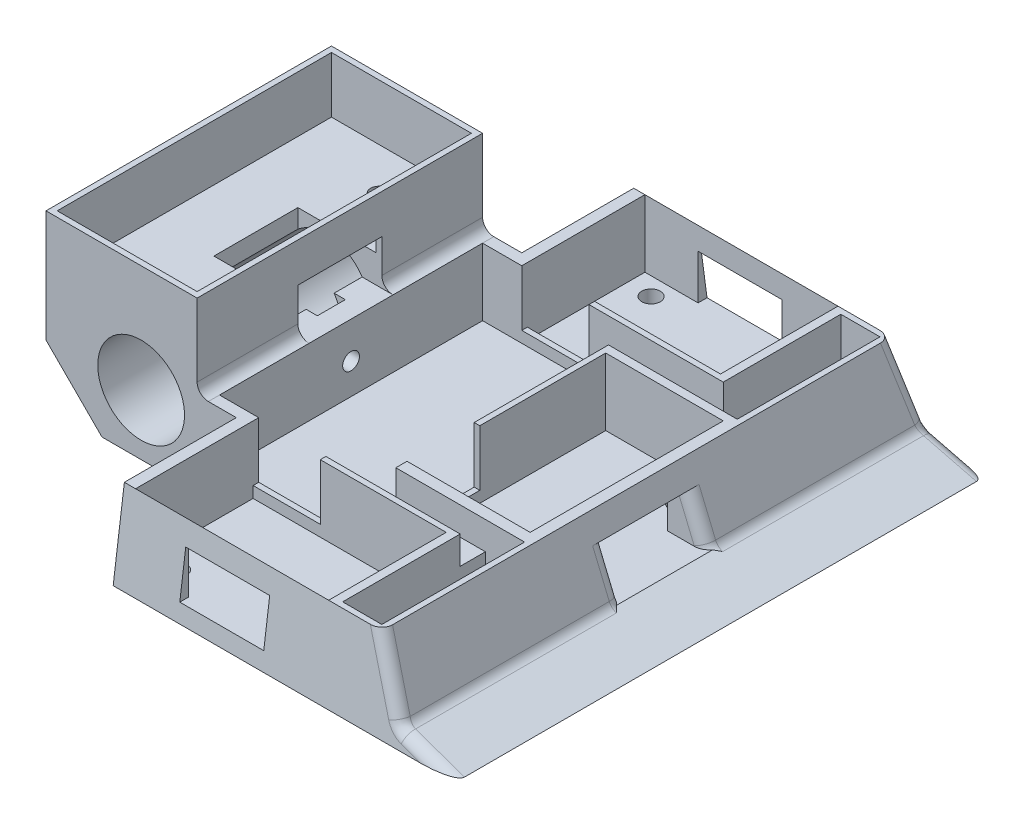
SolidWorks part; units mm, degrees
ref_plane "Front Plane" through (0, 0, 0) normal (0, 0, 1) x (1, 0, 0)
ref_plane "Top Plane" through (0, 0, 0) normal (0, 1, 0) x (1, 0, 0)
ref_plane "Right Plane" through (0, 0, 0) normal (1, 0, 0) x (0, 0, -1)
sketch "Sketch1" plane through (0, 0, 0) normal (0, 1, 0) x (1, 0, 0)
  line L1 (-26.0319, 60.4179) -> (68.9681, 60.4179)
  line L2 (-26.0319, 60.4179) -> (-26.0319, -34.5821)
  line L3 (-26.0319, -34.5821) -> (68.9681, -34.5821)
  line L4 (68.9681, 60.4179) -> (68.9681, -34.5821)
  dimension "D1" = 95
  dimension "D2" = 95
extrude "Boss-Extrude1" add sketch "Sketch1" along normal blind 20
sketch "Sketch2" plane through (0, 0, 34.5821) normal (0, 0, 1) x (1, 0, 0)
  line L0 (-26.0319, 20) -> (68.9681, 20) construction
  line L1 (-26.0319, 0) -> (7.9681, 0)
  line L2 (-26.0319, 0) -> (-26.0319, 20)
  line L3 (-26.0319, 20) -> (7.9681, 20)
  line L4 (7.9681, 0) -> (7.9681, 20)
  dimension "D1" = 34
extrude "Cut-Extrude1" cut sketch "Sketch2" against normal blind 22
sketch "Sketch3" plane through (0, 0, -60.4179) normal (0, 0, -1) x (-1, 0, 0)
  line L0 (-68.9681, 20) -> (26.0319, 20) construction
  line L1 (26.0319, 0) -> (-7.9681, 0)
  line L2 (26.0319, 0) -> (26.0319, 20)
  line L3 (26.0319, 20) -> (-7.9681, 20)
  line L4 (-7.9681, 0) -> (-7.9681, 20)
  dimension "D1" = 34
extrude "Cut-Extrude2" cut sketch "Sketch3" against normal blind 22
sketch "Sketch4" plane through (0, 0, -38.4179) normal (0, 0, -1) x (-1, 0, 0)
  line L0 (-7.9681, 0) -> (26.0319, 0) construction
  line L1 (26.0319, 0) -> (26.0319, 20) construction
  circle A0 centre (9.0319, 10.75) radius 7.75
  dimension "D1" = 10.75
  dimension "D2" = 17
extrude "Cut-Extrude3" cut sketch "Sketch4" against normal blind 100
sketch "Sketch5" plane through (0, 0, -60.4179) normal (0, 0, -1) x (-1, 0, 0)
  line L0 (-7.9681, 20) -> (-7.9681, 0) construction
  line L1 (-68.9681, 20) -> (-7.9681, 20)
  line L2 (-68.9681, 20) -> (-68.9681, 15)
  line L3 (-68.9681, 15) -> (-7.9681, 15)
  line L4 (-7.9681, 20) -> (-7.9681, 15)
  dimension "D1" = 5
extrude "Cut-Extrude4" cut sketch "Sketch5" against normal blind 100
fillet "Fillet3" radius 2 2 edges at (7.9681, 15, -12.9179) (7.9681, 20, -12.9179)
sketch "Sketch7" plane through (68.9681, 0, 0) normal (1, 0, 0) x (0, 0, -1)
  line L0 (-34.5821, 0) -> (60.4179, 0) construction
  line L1 (5.4179, 3) -> (20.4179, 3)
  line L2 (5.4179, 3) -> (5.4179, 11)
  line L3 (5.4179, 11) -> (20.4179, 11)
  line L4 (20.4179, 3) -> (20.4179, 11)
  line L5 (-34.5821, 15) -> (-34.5821, 0) construction
  line L6 (60.4179, 15) -> (60.4179, 0) construction
  dimension "D1" = 15
  dimension "D2" = 8
  dimension "D3" = 3
  dimension "D4" = 40
  dimension "D5" = 40
extrude "Cut-Extrude7" cut sketch "Sketch7" against normal blind 50
sketch "Sketch8" plane through (0, 0, 34.5821) normal (0, 0, 1) x (1, 0, 0)
  line L0 (68.9681, 0) -> (58.9681, 3)
  line L1 (58.9681, 3) -> (53.9681, 15)
  line L2 (68.9681, 15) -> (7.9681, 15) construction
  line L3 (53.9681, 15) -> (68.9681, 15)
  line L4 (68.9681, 15) -> (68.9681, 0)
  line L6 (7.9681, 0) -> (68.9681, 0) construction
  dimension "D1" = 15
  dimension "D2" = 10
  dimension "D3" = 3
extrude "Cut-Extrude8" cut sketch "Sketch8" against normal blind 100
fillet "Fillet4" radius 2 1 edges at (58.9681, 3, 14.5821)
fillet "Fillet5" radius 2 1 edges at (58.9681, 3, -40.4179)
sketch "Sketch10" plane through (0, 15, 0) normal (0, 1, 0) x (1, 0, 0)
  line L0 (53.9681, 60.4179) -> (53.9681, -34.5821) construction
  line L1 (51.9681, -4.0821) -> (30.9681, -4.0821)
  line L2 (51.9681, -4.0821) -> (51.9681, 29.9179)
  line L3 (51.9681, 29.9179) -> (30.9681, 29.9179)
  line L4 (30.9681, -4.0821) -> (30.9681, 29.9179)
  dimension "D1" = 9.5
  dimension "D2" = 34
  dimension "D3" = 21
  dimension "D4" = 9.5
  dimension "D5" = 2
extrude "Cut-Extrude9" cut sketch "Sketch10" against normal blind 12
sketch "Sketch11" plane through (0, 15, 0) normal (0, 1, 0) x (1, 0, 0)
  line L0 (7.9681, -34.5821) -> (7.9681, -12.5821) construction
  line L1 (9.9681, -32.5821) -> (43.9681, -32.5821)
  line L2 (9.9681, -32.5821) -> (9.9681, -11.5821)
  line L3 (9.9681, -11.5821) -> (43.9681, -11.5821)
  line L4 (43.9681, -32.5821) -> (43.9681, -11.5821)
  line L5 (53.9681, -34.5821) -> (7.9681, -34.5821) construction
  line L6 (53.9681, 60.4179) -> (7.9681, 60.4179) construction
  line L7 (9.9681, 58.4179) -> (43.9681, 58.4179)
  line L8 (9.9681, 58.4179) -> (9.9681, 37.4179)
  line L9 (9.9681, 37.4179) -> (43.9681, 37.4179)
  line L10 (43.9681, 58.4179) -> (43.9681, 37.4179)
  dimension "D1" = 21
  dimension "D2" = 34
  dimension "D3" = 2
  dimension "D4" = 2
  dimension "D5" = 21
  dimension "D6" = 2
extrude "Cut-Extrude10" cut sketch "Sketch11" against normal blind 12
sketch "Sketch12" plane through (0, 0, 34.5821) normal (0, 0, 1) x (1, 0, 0)
  line L0 (7.9681, 0) -> (68.9681, 0) construction
  line L1 (19.4681, 3) -> (34.4681, 3)
  line L2 (19.4681, 3) -> (19.4681, 11)
  line L3 (19.4681, 11) -> (34.4681, 11)
  line L4 (34.4681, 3) -> (34.4681, 11)
  dimension "D1" = 8
  dimension "D2" = 15
  dimension "D3" = 3
  dimension "D4" = 9.5
  dimension "D5" = 9.5
extrude "Cut-Extrude11" cut sketch "Sketch12" against normal blind 20
sketch "Sketch13" plane through (0, 0, -60.4179) normal (0, 0, -1) x (-1, 0, 0)
  line L0 (-68.9681, 0) -> (-7.9681, 0) construction
  line L1 (-19.4681, 3) -> (-34.4681, 3)
  line L2 (-19.4681, 3) -> (-19.4681, 11)
  line L3 (-19.4681, 11) -> (-34.4681, 11)
  line L4 (-34.4681, 3) -> (-34.4681, 11)
  dimension "D1" = 15
  dimension "D2" = 8
  dimension "D3" = 3
  dimension "D4" = 9.5
extrude "Cut-Extrude12" cut sketch "Sketch13" against normal blind 20
sketch "Sketch14" plane through (7.9681, 0, 0) normal (1, 0, 0) x (0, 0, -1)
  line L0 (38.4179, 15) -> (60.4179, 15) construction
  line L1 (38.7091, 15) -> (-20.22, 15)
  line L2 (38.7091, 15) -> (38.7091, 30.0235)
  line L3 (38.7091, 30.0235) -> (-20.22, 30.0235)
  line L4 (-20.22, 15) -> (-20.22, 30.0235)
extrude "Cut-Extrude13" cut sketch "Sketch14" against normal blind 10 and the other way blind 10
sketch "Sketch15" plane through (-2.0319, 0, 0) normal (1, 0, 0) x (0, 0, -1)
  line L1 (-12.5821, 15) -> (38.4179, 15)
  line L2 (-12.5821, 15) -> (-12.5821, 20)
  line L3 (-12.5821, 20) -> (38.4179, 20)
  line L4 (38.4179, 15) -> (38.4179, 20)
extrude "Boss-Extrude2" add sketch "Sketch15" along normal blind 3
sketch "Sketch16" plane through (0, 15, 0) normal (0, 1, 0) x (1, 0, 0)
  line L0 (0.9681, -12.5821) -> (0.9681, 38.4179) construction
  line L1 (2.9681, -10.5821) -> (29.9681, -10.5821)
  line L2 (2.9681, -10.5821) -> (2.9681, 36.4179)
  line L3 (2.9681, 36.4179) -> (29.9681, 36.4179)
  line L4 (29.9681, -10.5821) -> (29.9681, 36.4179)
  line L5 (43.9681, -11.5821) -> (9.9681, -11.5821) construction
  line L6 (9.9681, 37.4179) -> (43.9681, 37.4179) construction
  dimension "D1" = 2
  dimension "D2" = 1
  dimension "D3" = 1
  dimension "D4" = 1
extrude "Cut-Extrude14" cut sketch "Sketch16" against normal blind 12
sketch "Sketch17" plane through (0, 3, 0) normal (0, 1, 0) x (1, 0, 0)
  line L1 (30.9681, 5.4179) -> (29.9681, 5.4179)
  line L2 (30.9681, 5.4179) -> (30.9681, 20.4179)
  line L3 (30.9681, 20.4179) -> (29.9681, 20.4179)
  line L4 (29.9681, 5.4179) -> (29.9681, 20.4179)
extrude "Boss-Extrude3" add sketch "Sketch17" along normal blind 12
sketch "Sketch18" plane through (0, 15, 0) normal (0, 1, 0) x (1, 0, 0)
  line L0 (2.9681, -10.5821) -> (29.9681, -10.5821) construction
  line L1 (9.9681, -11.5821) -> (21.9681, -11.5821)
  line L2 (9.9681, -11.5821) -> (9.9681, -10.5821)
  line L3 (9.9681, -10.5821) -> (21.9681, -10.5821)
  line L4 (21.9681, -11.5821) -> (21.9681, -10.5821)
  dimension "D1" = 12
extrude "Cut-Extrude15" cut sketch "Sketch18" against normal blind 10
sketch "Sketch19" plane through (0, 15, 0) normal (0, 1, 0) x (1, 0, 0)
  line L0 (29.9681, 36.4179) -> (2.9681, 36.4179) construction
  line L1 (21.9681, 36.4179) -> (9.9681, 36.4179)
  line L2 (21.9681, 36.4179) -> (21.9681, 37.4179)
  line L3 (21.9681, 37.4179) -> (9.9681, 37.4179)
  line L4 (9.9681, 36.4179) -> (9.9681, 37.4179)
  dimension "D1" = 12
extrude "Cut-Extrude16" cut sketch "Sketch19" against normal blind 10
sketch "Sketch20" plane through (0, 15, 0) normal (0, 1, 0) x (1, 0, 0)
  line L0 (29.9681, -10.5821) -> (29.9681, 36.4179) construction
  line L1 (30.9681, -4.0821) -> (29.9681, -4.0821)
  line L2 (30.9681, -4.0821) -> (30.9681, 7.9179)
  line L3 (30.9681, 7.9179) -> (29.9681, 7.9179)
  line L4 (29.9681, -4.0821) -> (29.9681, 7.9179)
  dimension "D1" = 12
extrude "Cut-Extrude17" cut sketch "Sketch20" against normal blind 10
sketch "Sketch21" plane through (0, 0, 0) normal (0, -1, 0) x (-1, 0, 0)
  line L0 (-68.9681, -34.5821) -> (-68.9681, 60.4179) construction
  line L1 (-56.9681, 58.4179) -> (-46.9681, 58.4179)
  line L2 (-56.9681, 58.4179) -> (-56.9681, 38.4179)
  line L3 (-56.9681, 38.4179) -> (-46.9681, 38.4179)
  line L4 (-46.9681, 58.4179) -> (-46.9681, 38.4179)
  line L5 (-68.9681, 60.4179) -> (-7.9681, 60.4179) construction
  line L6 (-7.9681, -34.5821) -> (-68.9681, -34.5821) construction
  line L7 (-56.9681, -32.5821) -> (-46.9681, -32.5821)
  line L8 (-56.9681, -32.5821) -> (-56.9681, -12.5821)
  line L9 (-56.9681, -12.5821) -> (-46.9681, -12.5821)
  line L10 (-46.9681, -32.5821) -> (-46.9681, -12.5821)
  dimension "D1" = 10
  dimension "D2" = 10
  dimension "D3" = 20
  dimension "D4" = 12
  dimension "D5" = 2
  dimension "D6" = 20
  dimension "D7" = 2
extrude "Cut-Extrude18" cut sketch "Sketch21" against normal blind 4
sketch "Sketch22" plane through (0, 4, 0) normal (0, -1, 0) x (-1, 0, 0)
  line L0 (-46.9681, 38.4179) -> (-46.9681, 58.4179) construction
  line L1 (-54.4681, 54.4179) -> (-49.4681, 54.4179)
  line L2 (-54.4681, 54.4179) -> (-54.4681, 57.4179)
  line L3 (-54.4681, 57.4179) -> (-49.4681, 57.4179)
  line L4 (-49.4681, 54.4179) -> (-49.4681, 57.4179)
  line L5 (-46.9681, 58.4179) -> (-56.9681, 58.4179) construction
  line L6 (-56.9681, -32.5821) -> (-46.9681, -32.5821) construction
  line L7 (-54.4681, -31.5821) -> (-49.4681, -31.5821)
  line L8 (-54.4681, -31.5821) -> (-54.4681, -28.5821)
  line L9 (-54.4681, -28.5821) -> (-49.4681, -28.5821)
  line L10 (-49.4681, -31.5821) -> (-49.4681, -28.5821)
  dimension "D1" = 5
  dimension "D2" = 2.5
  dimension "D3" = 1
  dimension "D4" = 3
  dimension "D5" = 3
  dimension "D6" = 1
extrude "Cut-Extrude23" cut sketch "Sketch22" against normal blind 8
sketch "Sketch23" plane through (0, 15, 0) normal (0, 1, 0) x (1, 0, 0)
  line L0 (53.9681, 60.4179) -> (53.9681, -34.5821) construction
  line L1 (52.9681, -32.5821) -> (45.9681, -32.5821)
  line L2 (52.9681, -32.5821) -> (52.9681, -6.0821)
  line L3 (52.9681, -6.0821) -> (45.9681, -6.0821)
  line L4 (45.9681, -32.5821) -> (45.9681, -6.0821)
  line L5 (53.9681, -34.5821) -> (7.9681, -34.5821) construction
  line L6 (29.9681, -4.0821) -> (51.9681, -4.0821) construction
  line L7 (43.9681, -32.5821) -> (43.9681, -11.5821) construction
  dimension "D1" = 1
  dimension "D2" = 2
  dimension "D3" = 2
  dimension "D4" = 2
extrude "Cut-Extrude24" cut sketch "Sketch23" against normal blind 8
sketch "Sketch24" plane through (0, 15, 0) normal (0, 1, 0) x (1, 0, 0)
  line L0 (51.9681, 29.9179) -> (30.9681, 29.9179) construction
  line L1 (45.9681, 58.4179) -> (52.9681, 58.4179)
  line L2 (45.9681, 58.4179) -> (45.9681, 31.9179)
  line L3 (45.9681, 31.9179) -> (52.9681, 31.9179)
  line L4 (52.9681, 58.4179) -> (52.9681, 31.9179)
  line L5 (53.9681, 60.4179) -> (53.9681, -34.5821) construction
  line L6 (53.9681, 60.4179) -> (7.9681, 60.4179) construction
  line L7 (43.9681, 37.4179) -> (43.9681, 58.4179) construction
  dimension "D1" = 2
  dimension "D2" = 1
  dimension "D3" = 2
  dimension "D4" = 2
extrude "Cut-Extrude25" cut sketch "Sketch24" against normal blind 8
sketch "Sketch25" plane through (0, 15, 0) normal (0, 1, 0) x (1, 0, 0)
  line L1 (45.9681, 31.9179) -> (29.9681, 31.9179)
  line L2 (45.9681, 31.9179) -> (45.9681, 36.4179)
  line L3 (45.9681, 36.4179) -> (29.9681, 36.4179)
  line L4 (29.9681, 31.9179) -> (29.9681, 36.4179)
extrude "Cut-Extrude26" cut sketch "Sketch25" against normal blind 5
sketch "Sketch27" plane through (0, 15, 0) normal (0, 1, 0) x (1, 0, 0)
  line L1 (29.9681, -10.5821) -> (45.9681, -10.5821)
  line L2 (29.9681, -10.5821) -> (29.9681, -6.0821)
  line L3 (29.9681, -6.0821) -> (45.9681, -6.0821)
  line L4 (45.9681, -10.5821) -> (45.9681, -6.0821)
extrude "Cut-Extrude27" cut sketch "Sketch27" against normal blind 5
chamfer "Chamfer1" distance 10 angle 45 1 edges at (-26.0319, 0, -12.9179)
sketch "Sketch28" plane through (0, 20, 0) normal (0, 1, 0) x (1, 0, 0)
  line L1 (-26.0319, 38.4179) -> (0.9681, 38.4179)
  line L2 (-26.0319, 38.4179) -> (-26.0319, -12.5821)
  line L3 (-26.0319, -12.5821) -> (0.9681, -12.5821)
  line L4 (0.9681, 38.4179) -> (0.9681, -12.5821)
extrude "Boss-Extrude4" add sketch "Sketch28" along normal blind 10
sketch "Sketch29" plane through (0, 30, 0) normal (0, 1, 0) x (1, 0, 0)
  line L0 (-26.0319, 38.4179) -> (-26.0319, -12.5821) construction
  line L1 (-0.0319, -11.5821) -> (-25.0319, -11.5821)
  line L2 (-0.0319, -11.5821) -> (-0.0319, 37.4179)
  line L3 (-0.0319, 37.4179) -> (-25.0319, 37.4179)
  line L4 (-25.0319, -11.5821) -> (-25.0319, 37.4179)
  line L5 (0.9681, 38.4179) -> (-26.0319, 38.4179) construction
  line L6 (0.9681, -12.5821) -> (0.9681, 38.4179) construction
  line L7 (-26.0319, -12.5821) -> (0.9681, -12.5821) construction
  dimension "D1" = 1
  dimension "D2" = 1
  dimension "D3" = 1
  dimension "D4" = 1
extrude "Cut-Extrude28" cut sketch "Sketch29" against normal blind 10
sketch "Sketch30" plane through (0.9681, 0, 0) normal (1, 0, 0) x (0, 0, -1)
  line L0 (-12.5821, 15) -> (38.4179, 15) construction
  line L1 (5.4179, 15) -> (20.4179, 15)
  line L2 (5.4179, 15) -> (5.4179, 23)
  line L3 (5.4179, 23) -> (20.4179, 23)
  line L4 (20.4179, 15) -> (20.4179, 23)
  line L5 (38.4179, 15) -> (38.4179, 30) construction
  line L6 (-12.5821, 30) -> (-12.5821, 15) construction
  dimension "D1" = 15
  dimension "D2" = 8
  dimension "D3" = 18
  dimension "D4" = 18
extrude "Cut-Extrude30" cut sketch "Sketch30" against normal blind 15
fillet "Fillet7" radius 2 2 edges at (0.9681, 15, 3.5821) (0.9681, 15, -29.4179)
sketch "Sketch31" plane through (7.9681, 0, 0) normal (-1, 0, 0) x (0, 0, 1)
  line L0 (34.5821, 0) -> (32.5821, 15)
  line L1 (34.5821, 15) -> (12.5821, 15) construction
  line L2 (34.5821, 15) -> (34.5821, 0)
  line L3 (32.5821, 15) -> (34.5821, 15)
  dimension "D1" = 2
extrude "Cut-Extrude31" cut sketch "Sketch31" against normal blind 100
sketch "Sketch32" plane through (0, 7, 0) normal (0, 1, 0) x (1, 0, 0)
  line L1 (52.9681, -31.5821) -> (45.9681, -31.5821)
  line L2 (52.9681, -31.5821) -> (52.9681, -32.5821)
  line L3 (52.9681, -32.5821) -> (45.9681, -32.5821)
  line L4 (45.9681, -31.5821) -> (45.9681, -32.5821)
extrude "Boss-Extrude5" add sketch "Sketch32" along normal blind 8
sketch "Sketch33" plane through (7.9681, 0, 0) normal (-1, 0, 0) x (0, 0, 1)
  line L0 (-60.4179, 0) -> (-58.4179, 15)
  line L1 (-38.4179, 15) -> (-60.4179, 15) construction
  line L2 (-58.4179, 15) -> (-60.4179, 15)
  line L3 (-60.4179, 15) -> (-60.4179, 0)
  dimension "D1" = 2
extrude "Cut-Extrude32" cut sketch "Sketch33" against normal blind 100
sketch "Sketch34" plane through (0, 7, 0) normal (0, 1, 0) x (1, 0, 0)
  line L1 (52.9681, 57.4179) -> (45.9681, 57.4179)
  line L2 (52.9681, 57.4179) -> (52.9681, 58.4179)
  line L3 (52.9681, 58.4179) -> (45.9681, 58.4179)
  line L4 (45.9681, 57.4179) -> (45.9681, 58.4179)
extrude "Boss-Extrude6" add sketch "Sketch34" along normal blind 8
sketch "Sketch35" plane through (0, 15, 0) normal (0, 1, 0) x (1, 0, 0)
  line L0 (-2.5512, 5.4179) -> (-2.5512, 20.4179) construction
  line L1 (-2.5512, 15.4179) -> (-0.5512, 15.4179)
  line L3 (-2.5512, 10.4179) -> (-0.5512, 10.4179)
  line L4 (-0.5512, 15.4179) -> (-0.5512, 10.4179)
  line L5 (-2.5512, 20.4179) -> (2.9681, 20.4179) construction
  line L7 (-2.5512, 15.4179) -> (-5.5512, 15.4179)
  line L9 (-2.5512, 10.4179) -> (-5.5512, 10.4179)
  line L10 (-5.5512, 15.4179) -> (-5.5512, 10.4179)
  dimension "D1" = 5
  dimension "D2" = 2
  dimension "D3" = 5
  dimension "D4" = 5
  dimension "D5" = 3
extrude "Cut-Extrude33" cut sketch "Sketch35" against normal blind 8
sketch "Sketch36" plane through (2.9681, 0, 0) normal (1, 0, 0) x (0, 0, -1)
  line L0 (36.4179, 3) -> (36.4179, 15) construction
  line L1 (-10.5821, 3) -> (-10.5821, 15) construction
  circle A0 centre (12.9179, 8.4965) radius 1.5
  point P4 (-10.5821, 9)
  dimension "D1" = 23.5
  dimension "D2" = 23.5
extrude "Cut-Extrude34" cut sketch "Sketch36" against normal blind 10
sketch "Sketch37" plane through (0, 7, 0) normal (0, 1, 0) x (1, 0, 0)
  line L1 (-0.5512, 15.4179) -> (-2.2496, 15.4179)
  line L2 (-0.5512, 15.4179) -> (-0.5512, 10.4179)
  line L3 (-0.5512, 10.4179) -> (-2.2496, 10.4179)
  line L5 (-2.2496, 15.4179) -> (-4.346, 15.4179)
  line L7 (-2.2496, 10.4179) -> (-4.346, 10.4179)
  line L8 (-4.346, 15.4179) -> (-4.346, 10.4179)
extrude "Cut-Extrude35" cut sketch "Sketch37" against normal blind 3
sketch "Sketch39" plane through (0, 4, 0) normal (0, -1, 0) x (-1, 0, 0)
  line L0 (-46.9681, -32.5821) -> (-46.9681, -12.5821) construction
  line L1 (-56.9681, -12.5821) -> (-56.9681, -32.5821) construction
  line L2 (-46.9681, -12.5821) -> (-56.9681, -12.5821) construction
  line L3 (-56.9681, 38.4179) -> (-46.9681, 38.4179) construction
  circle A0 centre (-51.9681, -17.5821) radius 0.6
  circle A1 centre (-51.9681, 43.4179) radius 0.6
  dimension "D1" = 5
  dimension "D4" = 5
  dimension "D2" = 5
  dimension "D3" = 5
extrude "Cut-Extrude36" cut sketch "Sketch39" against normal blind 10
sketch "Sketch40" plane through (0, 3, 0) normal (0, 1, 0) x (1, 0, 0)
  line L0 (9.9681, -32.5821) -> (19.4681, -32.5821) construction
  line L1 (9.9681, -11.5821) -> (9.9681, -32.5821) construction
  line L2 (43.9681, -32.5821) -> (43.9681, -11.5821) construction
  line L3 (43.9681, 58.4179) -> (9.9681, 58.4179) construction
  circle A0 centre (14.2681, -29.3821) radius 1.65
  circle A1 centre (39.6681, -29.3821) radius 1.65
  circle A2 centre (14.2681, 55.2179) radius 1.65
  circle A3 centre (39.6681, 55.2179) radius 1.65
  point P2 (14.7181, -32.5821)
  dimension "D1" = 3.2
  dimension "D2" = 3.3
  dimension "D6" = 3.2
  dimension "D3" = 25.4
  dimension "D4" = 4.3
  dimension "D5" = 4.3
  dimension "D7" = 3.2
extrude "Cut-Extrude37" cut sketch "Sketch40" against normal blind 10
sketch "Sketch41" plane through (0, 3, 0) normal (0, 1, 0) x (1, 0, 0)
  line L0 (51.9681, 29.9179) -> (30.9681, 29.9179) construction
  line L1 (51.9681, 20.4179) -> (51.9681, 29.9179) construction
  line L2 (29.9681, -4.0821) -> (51.9681, -4.0821) construction
  line L3 (51.9681, -4.0821) -> (51.9681, 5.4179) construction
  circle A0 centre (48.7681, 25.6179) radius 1.65
  circle A1 centre (48.7681, 0.2179) radius 1.65
  point P4 (51.9681, 25.1679)
  point P11 (51.9681, 0.6679)
  dimension "D1" = 4.3
  dimension "D3" = 4.3
  dimension "D2" = 3.2
  dimension "D4" = 25.4
extrude "Cut-Extrude38" cut sketch "Sketch41" against normal blind 10
sketch "Sketch42" plane through (43.9681, 0, 0) normal (-1, 0, 0) x (0, 0, 1)
  line L1 (11.5821, 15) -> (32.5821, 15)
  line L2 (11.5821, 15) -> (11.5821, 3)
  line L3 (11.5821, 3) -> (32.5821, 3)
  line L4 (32.5821, 15) -> (32.5821, 3)
extrude "Cut-Extrude39" cut sketch "Sketch42" against normal blind 0.5
sketch "Sketch43" plane through (43.9681, 0, 0) normal (-1, 0, 0) x (0, 0, 1)
  line L1 (-37.4179, 3) -> (-58.4179, 3)
  line L2 (-37.4179, 3) -> (-37.4179, 15)
  line L3 (-37.4179, 15) -> (-58.4179, 15)
  line L4 (-58.4179, 3) -> (-58.4179, 15)
extrude "Cut-Extrude40" cut sketch "Sketch43" against normal blind 0.5
sketch "Sketch44" plane through (0, 0, -29.9179) normal (0, 0, 1) x (1, 0, 0)
  line L1 (30.9681, 3) -> (51.9681, 3)
  line L2 (30.9681, 3) -> (30.9681, 15)
  line L3 (30.9681, 15) -> (51.9681, 15)
  line L4 (51.9681, 3) -> (51.9681, 15)
extrude "Cut-Extrude41" cut sketch "Sketch44" against normal blind 0.5
fillet "Fillet9" radius 2 10 edges at (57.1193, 7.4371, -20.4179) (64.4217, 1.3639, -60.236) (56.286, 9.4371, -59.1596) (57.1193, 7.4371, -5.4179) (56.286, 9.4371, 33.3238) (64.4217, 1.3639, 34.4003) (59.1107, 3.1581, -20.4179) (59.1107, 3.1581, -59.9968) (59.1107, 3.1581, -5.4179) (59.1107, 3.1581, 34.161)
sketch "Sketch46" plane through (0, 20, 0) normal (0, 1, 0) x (1, 0, 0)
  line L0 (-25.0319, -11.5821) -> (-0.0319, -11.5821) construction
  line L1 (-0.0319, 37.4179) -> (-25.0319, 37.4179) construction
  circle A0 centre (-9.0319, 29.9179) radius 1.5
  circle A3 centre (-9.0319, -4.0821) radius 1.5
  dimension "D5" = 3
  dimension "D6" = 3
  dimension "D1" = 7.75
  dimension "D2" = 7.75
  dimension "D3" = 7.5
  dimension "D4" = 7.5
extrude "Cut-Extrude43" cut sketch "Sketch46" against normal blind 10
sketch "Sketch47" plane through (-8.0159, -8.0159, 0) normal (-0.7071, -0.7071, 0) x (-0.7071, 0.7071, 0)
  line L0 (25.4784, 38.4179) -> (25.4784, -12.5821) construction
  line L1 (25.4784, -12.5821) -> (11.3363, -12.5821) construction
  circle A0 centre (18.4084, 23.4179) radius 1.5
  circle A1 centre (18.4088, 2.4179) radius 1.5
  point P7 (18.4073, -12.5821)
  dimension "D4" = 3
  dimension "D5" = 3
  dimension "D1" = 7.07
  dimension "D2" = 15
  dimension "D3" = 15
extrude "Cut-Extrude44" cut sketch "Sketch47" against normal blind 10
